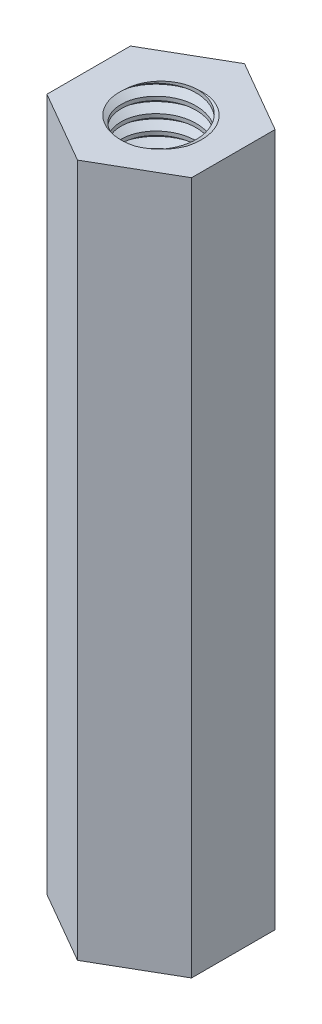
SolidWorks part; units mm, degrees
ref_plane "Front Plane" through (0, 0, 0) normal (0, 0, 1) x (1, 0, 0)
ref_plane "Top Plane" through (0, 0, 0) normal (0, 1, 0) x (1, 0, 0)
ref_plane "Right Plane" through (0, 0, 0) normal (1, 0, 0) x (0, 0, -1)
sketch "Sketch1" plane through (0, 0, 0) normal (0, 1, 0) x (1, 0, 0)
  line L1 (2.4, 1.3856) -> (0, 2.7713)
  line L2 (0, 2.7713) -> (-2.4, 1.3856)
  line L3 (-2.4, 1.3856) -> (-2.4, -1.3856)
  line L4 (-2.4, -1.3856) -> (0, -2.7713)
  line L5 (0, -2.7713) -> (2.4, -1.3856)
  line L6 (2.4, -1.3856) -> (2.4, 1.3856)
  circle A0 centre (0, 0) radius 2.4 construction
  circle A1 centre (0, 0) radius 1.25
  dimension "D1" = 4.8
  dimension "D2" = 2.5
extrude "Boss-Extrude1" add sketch "Sketch1" along normal mid plane 23
thread "Thread1" pitch 0.5 method cut profile "Thread Profile1" start angle 0, offset 2, length 32, pitch 0.5, diameter 2.5
ref_plane "Plane1" through (-1.25, 13.5, 0) normal (0, 0, 1) x (-1, 0, 0)
sketch "Thread Profile1" plane through (-1.25, 13.5, 0) normal (0, 0, 1) x (-1, 0, 0)
  line L0 (0, 0) -> (0, 0.5) construction
  line L1 (0, 0) -> (0.2706, 0.1562)
  line L2 (0.2706, 0.1562) -> (0.2706, 0.2187)
  line L3 (0.2706, 0.2187) -> (0, 0.375)
  line L4 (0.2706, 0.1875) -> (0, 0.1875) construction
  line L11 (0, 0) -> (0, 0.375)
  point P2 (0, 0)
  dimension "Pitch" = 0.5
  dimension "Profile_Angle" = 60
  dimension "Profile_Land" = 0.0625
  dimension "Profile_Height" = 0.2706
sketch "Sketch2" plane through (0, 0, 0) normal (0, 1, 0) x (1, 0, 0)
  line L6 (2.4, -1.3856) -> (2.4, 1.3856)
  line L7 (2.4, 1.3856) -> (0, 2.7713)
  line L8 (0, 2.7713) -> (-2.4, 1.3856)
  line L9 (-2.4, 1.3856) -> (-2.4, -1.3856)
  line L10 (-2.4, -1.3856) -> (0, -2.7713)
  line L11 (0, -2.7713) -> (2.4, -1.3856)
  line L12 (2.4, -1.3856) -> (2.4, 1.3856)
  line L13 (2.4, 1.3856) -> (0, 2.7713)
  line L14 (0, 2.7713) -> (-2.4, 1.3856)
  line L15 (-2.4, 1.3856) -> (-2.4, -1.3856)
  line L16 (-2.4, -1.3856) -> (0, -2.7713)
  line L17 (0, -2.7713) -> (2.4, -1.3856)
  dimension "D1" = 0
extrude "Boss-Extrude2" add sketch "Sketch2" along normal mid plane 12
